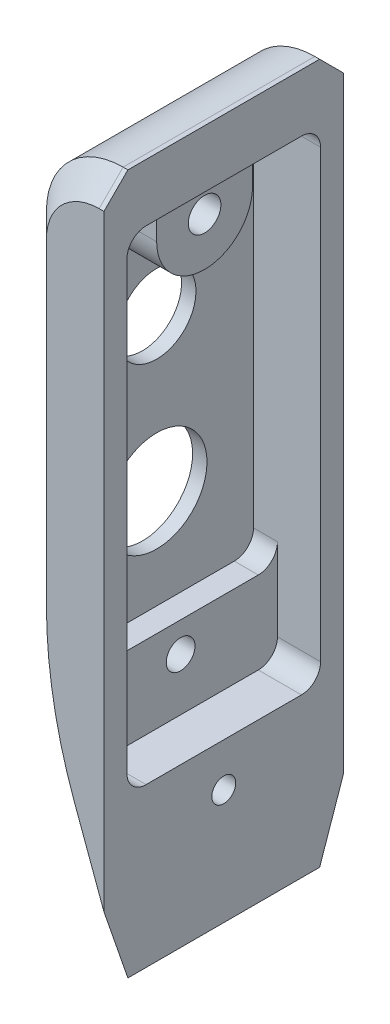
SolidWorks part; units mm, degrees
material "Сплав 2024"
ref_plane "Спереди" through (0, 0, 0) normal (0, 0, 1) x (1, 0, 0)
ref_plane "Сверху" through (0, 0, 0) normal (0, 1, 0) x (1, 0, 0)
ref_plane "Справа" through (0, 0, 0) normal (1, 0, 0) x (0, 0, -1)
sketch "Эскиз1" plane through (0, 0, 0) normal (0, 0, 1) x (1, 0, 0)
  line L0 (0, 0) -> (0, 73)
  line L1 (-0.5, 73) -> (0, 73)
  line L2 (-8.5, 65) -> (-8.5, 32)
  line L3 (-5.4214, 14.7261) -> (0, 0)
  arc A0 (-0.5, 73) -> (-8.5, 65) centre (-0.5, 65) ccw
  arc A1 (-8.5, 32) -> (-5.4214, 14.7261) centre (41.5, 32) ccw
  dimension "D2" = 50
  dimension "D5" = 8
  dimension "D1" = 8.5
  dimension "D3" = 73
  dimension "D4" = 33
  dimension "D6" = 8
extrude "Бобышка-Вытянуть1" add sketch "Эскиз1" along normal blind 25
chamfer "Фаска5" distance 2.5 angle 45 10 edges at (-0.25, 73, 0) (-2.7107, 7.3631, 0) (-6.1569, 70.6569, 0) (-7.7243, 23.227, 0) (-8.5, 48.5, 0) (-0.25, 73, 25) (-2.7107, 7.3631, 25) (-6.1569, 70.6569, 25) (-7.7243, 23.227, 25) (-8.5, 48.5, 25)
sketch "Эскиз6" plane through (0, 0, 0) normal (1, 0, 0) x (0, 0, -1)
  line L0 (-12.5, 73) -> (-12.5, 0) construction
  line L1 (-22.5, 73) -> (-2.5, 73) construction
  line L2 (-22.5, 0) -> (-2.5, 0) construction
  line L4 (-22.6, 67) -> (-2.4, 67)
  line L5 (-22.6, 67) -> (-22.6, 25.1087)
  line L6 (-22.6, 25.1087) -> (-2.4, 25.1087)
  line L7 (-2.4, 67) -> (-2.4, 25.1087)
  line L8 (-22.6, 67) -> (-2.4, 25.1087) construction
  line L9 (-22.6, 25.1087) -> (-2.4, 67) construction
  point P6 (-12.5, 46.0543)
  dimension "D1" = 20.2
  dimension "D2" = 6
  dimension "D3" = 25.1087
extrude "Вырез-Вытянуть2" cut sketch "Эскиз6" against normal offset from surface (7 mm away) 1.5 up to face at (-8.5, 48.5, 12.5)
sketch "Эскиз7" plane through (-8.5, 0, 0) normal (-1, 0, 0) x (0, 0, 1)
  line L0 (12.5, 65) -> (12.5, 25.4737) construction
  line L1 (22.5, 65) -> (2.5, 65) construction
  line L3 (22.5, 0) -> (2.5, 0) construction
  circle A0 centre (12.5, 35.5) radius 5.25
  circle A1 centre (12.5, 51.5) radius 4.1
  dimension "D1" = 10.5
  dimension "D2" = 8.2
  dimension "D3" = 35.5
  dimension "D4" = 16
extrude "Вырез-Вытянуть3" cut sketch "Эскиз7" against normal through all
ref_plane "Плоскость1" through (0, 0, 12.5) normal (0, 0, 1) x (1, 0, 0)
sketch "Эскиз8" plane through (0, 0, 0) normal (1, 0, 0) x (0, 0, -1)
  line L1 (-22.6, 25.1087) -> (-2.4, 25.1087)
  line L2 (-22.6, 25.1087) -> (-22.6, 16.5228)
  line L3 (-22.6, 16.5228) -> (-2.4, 16.5228)
  line L4 (-2.4, 25.1087) -> (-2.4, 16.5228)
extrude "Вырез-Вытянуть4" cut sketch "Эскиз8" against normal offset from surface (4.5 mm away) 2.5 up to face at (-7, 55.6, 12.5)
fillet "Скругление2" radius 2 6 edges at (-2.25, 16.5228, 2.4) (-2.25, 16.5228, 22.6) (-5.75, 25.1087, 22.6) (-5.75, 25.1087, 2.4) (-3.5, 67, 2.4) (-3.5, 67, 22.6)
sketch "Эскиз10" plane through (-8.5, 0, 0) normal (-1, 0, 0) x (0, 0, 1)
  line L0 (12.5, 35.5) -> (12.5, 15.9746) construction
  circle A0 centre (12.5, 22) radius 1.5
  dimension "D1" = 3
  dimension "D2" = 13.5
extrude "Вырез-Вытянуть5" cut sketch "Эскиз10" against normal up to next
sketch "Эскиз11" plane through (0, 0, 0) normal (1, 0, 0) x (0, 0, -1)
  line L0 (-12.5, 16.5228) -> (-12.5, 3.5837) construction
  line L1 (-4.4, 16.5228) -> (-20.6, 16.5228) construction
  line L2 (-22.5, 73) -> (-2.5, 73) construction
  point P4 (-12.5, 12)
  point P5 (-12.5, 73)
  dimension "D1" = 61
hole_wizard "Отверстие обработанное метчиком M3x0.51" positions "Эскиз13" profile "Эскиз12" tap size "M3x0.5" standard "Ansi Metric"
sketch "Эскиз13" plane through (0, 0, 0) normal (1, 0, 0) x (0, 0, -1)
  point P0 (-12.5, 12)
sketch "Эскиз12" plane through (0, 12, 12.5) normal (0, 1, 0) x (0, 0, -1)
  line L0 (0, 0) -> (0, 3.7511)
  line L1 (0, 3.7511) -> (1.25, 3)
  line L2 (1.25, 3) -> (1.25, 0)
  line L5 (1.25, 0) -> (0, 0)
  line L10 (0, 3.7511) -> (-1.25, 3) construction
  line L11 (0, -6.35) -> (0, 107.95) construction
  dimension "Диаметр сверла" = 2.5
  dimension "Глубина сверла" = 3
  dimension "Угол заточки сверла" = 118
cosmetic thread "Отверстие резьбы1" parameters "D1"=3, "D2"=3
sketch "Эскиз15" plane through (0, 0, 0) normal (1, 0, 0) x (0, 0, -1)
  line L0 (-12.5, 73) -> (-12.5, 67) construction
  line L1 (-22.5, 73) -> (-2.5, 73) construction
  line L2 (-4.4, 67) -> (-20.6, 67) construction
  point P6 (-12.5, 68)
  dimension "D1" = 5
sketch "Эскиз18" plane through (-8.5, 0, 0) normal (-1, 0, 0) x (0, 0, 1)
  line L0 (12.5, 65) -> (12.5, 72.0513) construction
  line L1 (22.5, 65) -> (2.5, 65) construction
  line L2 (22.5, 73) -> (2.5, 73) construction
  point P4 (12.5, 68)
  dimension "D1" = 5
sketch "Эскиз22" plane through (-7, 0, 0) normal (1, 0, 0) x (0, 0, -1)
  line L1 (-12.5, 67) -> (-12.5, 58.1189) construction
  line L2 (-20.6, 67) -> (-4.4, 67) construction
  line L3 (-17.5, 63) -> (-17.5, 67)
  line L4 (-4.4, 67) -> (-20.6, 67) construction
  line L5 (-17.5, 67) -> (-7.5, 67)
  line L6 (-7.5, 67) -> (-7.5, 63)
  arc A0 (-17.5, 63) -> (-7.5, 63) centre (-12.5, 63) ccw
  dimension "D1" = 10
  dimension "D2" = 4
extrude "Бобышка-Вытянуть3" add sketch "Эскиз22" along normal blind 5
fillet "Скругление3" radius 2 2 edges at (-4.5, 67, 7.5) (-4.5, 67, 17.5)
hole_wizard "Цековка для винта с внутренним шестигранником M32" positions "Эскиз24" profile "Эскиз23" counterbore size "M3" standard "Ansi Metric" end condition through all
sketch "Эскиз24" plane through (-8.5, 0, 0) normal (-1, 0, 0) x (0, 0, 1)
  point P0 (12.5, 63)
sketch "Эскиз23" plane through (-8.5, 63, 12.5) normal (0, 1, 0) x (0, 0, 1)
  line L0 (0, 0) -> (0, 8.5)
  line L1 (0, 8.5) -> (1.7, 8.5)
  line L3 (1.7, 8.5) -> (1.7, 2.5)
  line L4 (1.7, 2.5) -> (3.25, 2.5)
  line L5 (3.25, 2.5) -> (3.25, 0)
  line L7 (3.25, 0) -> (0, 0)
  line L11 (0, -6.35) -> (0, 107.95) construction
  dimension "Диаметр сквозного отверстия" = 3.4
  dimension "Глубина сквозного отверстия" = 8.5
  dimension "Диаметр цековки" = 6.5
  dimension "Глубина цековки" = 2.5
